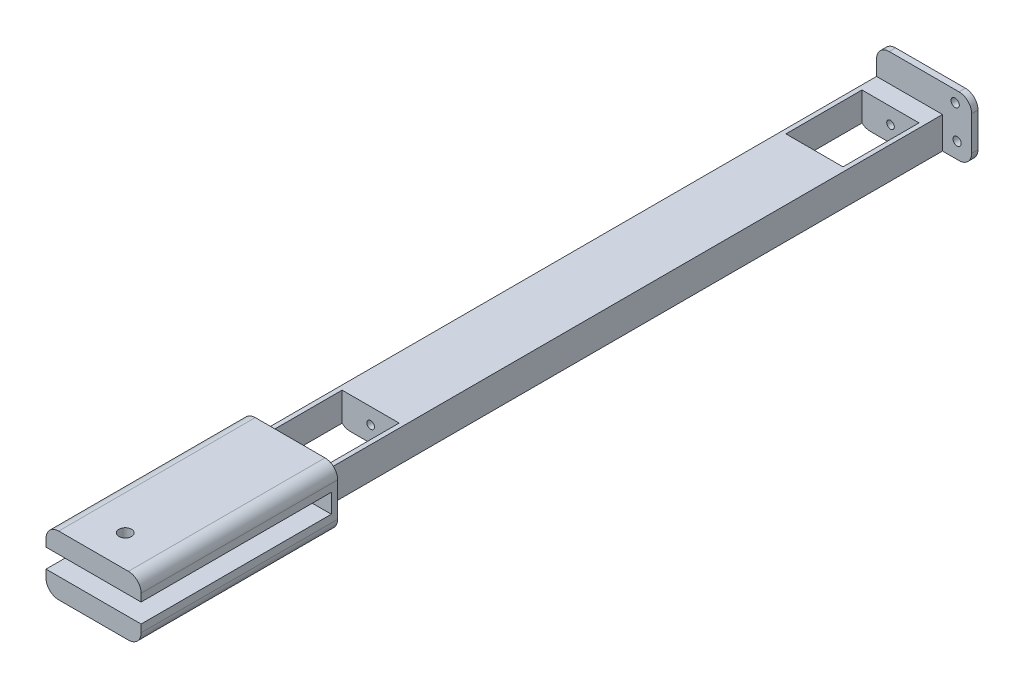
SolidWorks part; units mm, degrees
note: '?' marks a value the reader was unsure of.
material "Alloy Steel"
ref_plane "Front Plane" through (0, 0, 0) normal (0, 0, 1) x (1, 0, 0)
ref_plane "Top Plane" through (0, 0, 0) normal (0, 1, 0) x (1, 0, 0)
ref_plane "Right Plane" through (0, 0, 0) normal (1, 0, 0) x (0, 0, -1)
sketch "Sketch1" plane through (0, 0, 0) normal (0, 0, 1) x (1, 0, 0)
  line L1 (260, 125) -> (-260, 125)
  line L2 (260, 125) -> (260, -125)
  line L3 (260, -125) -> (-260, -125)
  line L4 (-260, 125) -> (-260, -125)
  line L5 (260, 125) -> (-260, -125) construction
  line L6 (260, -125) -> (-260, 125) construction
  point P0 (0, 0)
  dimension "D1" = 520
  dimension "D2" = 250
extrude "Boss-Extrude1" add sketch "Sketch1" along normal blind 5000
ref_plane "Plane1" through (0, 0, 4850) normal (0, 0, 1) x (1, 0, 0)
sketch "Sketch2" plane through (0, 0, 4850) normal (0, 0, 1) x (1, 0, 0)
  line L0 (-260, -125) -> (260, -125) construction
  line L1 (225, 125) -> (-225, 125)
  line L2 (225, 125) -> (225, -125)
  line L3 (225, -125) -> (-225, -125)
  line L4 (-225, 125) -> (-225, -125)
  line L5 (225, 125) -> (-225, -125) construction
  line L6 (225, -125) -> (-225, 125) construction
  line L8 (260, 125) -> (-260, 125) construction
  line L9 (-260, 125) -> (-260, -125) construction
  dimension "D1" = 450
  dimension "D2" = 35
extrude "Cut-Extrude1" cut sketch "Sketch2" against normal blind 600
ref_axis "Axis1" through (260, 125, 2500) along (-1, 0, 0)?
ref_plane "Plane2" through (0, 0, 2500) normal (0, 0, 1) x (1, 0, 0)
mirror "Mirror1" about plane through (0, 0, 2500) normal (0, 0, 1) of "Cut-Extrude1"
ref_plane "Plane3" through (0, 0, 5050) normal (0, 0, 1) x (1, 0, 0)
sketch "Sketch3" plane through (0, 0, 5000) normal (0, 0, 1) x (1, 0, 0)
  line L0 (-260, -125) -> (-260, 455)
  line L2 (490, -125) -> (-260, -125)
  line L4 (-260, 455) -> (490, 455)
  line L5 (490, 455) -> (490, -125)
  line L6 (260, 125) -> (-260, 125) construction
  line L7 (-260, 455) -> (490, 455)
  line L8 (-260, 455) -> (-260, 345)
  line L9 (-260, 345) -> (490, 345)
  line L10 (490, 455) -> (490, 345)
  dimension "D1" = 220
  dimension "D3" = 580
  dimension "D2" = 750
extrude "Boss-Extrude2" add sketch "Sketch3" along normal blind 50
sketch "Sketch4" plane through (0, 0, 5050) normal (0, 0, 1) x (1, 0, 0)
  line L0 (260, 125) -> (490, -125) construction
  line L1 (-260, 345) -> (490, 345) construction
  line L2 (490, 345) -> (490, -125) construction
  circle A2 centre (375, 0) radius 32.5
  circle A3 centre (360, 255) radius 32.5
  dimension "D1" = 65
  dimension "D2" = 65
  dimension "D3" = 130
  dimension "D4" = 90
extrude "Cut-Extrude2" cut sketch "Sketch4" against normal blind 50
mirror "Mirror2" about plane through (0, 0, 2500) normal (0, 0, 1) of "Boss-Extrude2", "Cut-Extrude2"
sketch "Sketch5" plane through (0, 0, 4850) normal (0, 0, -1) x (-1, 0, 0)
  circle A0 centre (0, 0) radius 30
  dimension "D1" = 60
extrude "Cut-Extrude3" cut sketch "Sketch5" against normal blind 170 and the other way through all
scale "Scale2" scale about centroid uniform scaling yes scale factor 0.1
fillet "Fillet1" radius 10 9 edges at (-16.1343, -6.1626, 2705.3593) (-16.1343, -6.1626, 2295.3593) (-19.6343, 40.8374, 2752.8593) (55.3657, -6.1626, 2752.8593) (55.3657, 40.8374, 2752.8593) (-19.6343, 40.8374, 2247.8593) (55.3657, 40.8374, 2247.8593) (55.3657, -6.1626, 2247.8593) (-19.6343, -6.1626, 2500.3593)
sketch "Sketch6" plane through (0, 0, 2755.3593) normal (0, 0, 1) x (1, 0, 0)
  line L0 (-9.6343, -6.1626) -> (45.3657, -6.1626)
  line L1 (-9.6343, 40.8374) -> (45.3657, 40.8374) construction
  line L3 (55.3657, 17.3374) -> (-18.253, 17.3374) construction
  line L4 (55.3657, 30.8374) -> (55.3657, 3.8374) construction
  line L5 (-9.6343, 40.8374) -> (45.3657, 40.8374)
  line L16 (55.3657, 3.8374) -> (55.3657, 9.8374)
  line L17 (-19.6343, 9.8374) -> (55.3657, 9.8374)
  line L21 (17.8657, 24.8374) -> (17.8657, 40.8374) construction
  line L22 (-19.6343, 24.8374) -> (55.3657, 24.8374)
  line L23 (-19.6343, 3.8374) -> (-19.6343, 30.8374) construction
  line L24 (55.3657, 30.8374) -> (55.3657, 24.8374)
  line L25 (-19.6343, 30.8374) -> (-19.6343, 24.8374)
  line L26 (-19.6343, 3.8374) -> (-19.6343, 9.8374)
  arc A0 (-9.6343, 40.8374) -> (-19.6343, 30.8374) centre (-9.6343, 30.8374) ccw construction
  arc A1 (55.3657, 30.8374) -> (45.3657, 40.8374) centre (45.3657, 30.8374) ccw construction
  arc A2 (-9.6343, 40.8374) -> (-19.6343, 30.8374) centre (-9.6343, 30.8374) ccw
  arc A3 (55.3657, 30.8374) -> (45.3657, 40.8374) centre (45.3657, 30.8374) ccw
  arc A4 (-9.6343, -6.1626) -> (-19.6343, 3.8374) centre (-9.6343, 3.8374) cw
  arc A5 (55.3657, 3.8374) -> (45.3657, -6.1626) centre (45.3657, 3.8374) cw
  dimension "D1" = 16
extrude "Boss-Extrude9" add sketch "Sketch6" along normal blind 150 and the other way blind 1 contours L25 L22 L24 A3 L5 A2 | A4 L26 L17 L16 A5 L0
sketch "Sketch7" plane through (0, 40.8374, 0) normal (0, 1, 0) x (1, 0, 0)
  line L0 (17.8657, -2750.3593) -> (17.8657, -2905.3593) construction
  line L1 (-9.6343, -2750.3593) -> (45.3657, -2750.3593) construction
  line L2 (-9.6343, -2905.3593) -> (45.3657, -2905.3593) construction
  line L3 (-9.6343, -2827.8593) -> (45.3657, -2827.8593) construction
  line L4 (-9.6343, -2750.3593) -> (-9.6343, -2905.3593) construction
  line L5 (45.3657, -2905.3593) -> (45.3657, -2750.3593) construction
  circle A0 centre (17.8657, -2880.3593) radius 5
  dimension "D1" = 10
  dimension "D2" = 25
extrude "Cut-Extrude4" cut sketch "Sketch7" against normal through all both and the other way through all
sketch "Sketch8" plane through (0, 0, 2754.3593) normal (0, 0, -1) x (-1, 0, 0)
  circle A1 centre (-42.3657, 31.8374) radius 3.25
  circle A2 centre (-42.3657, 31.8374) radius 3.25
  circle A3 centre (-43.8657, 6.3374) radius 3.25
  circle A4 centre (-43.8657, 6.3374) radius 3.25
  dimension "D1" = 0
  dimension "D2" = 0
extrude "Cut-Extrude5" cut sketch "Sketch8" against normal blind 20
